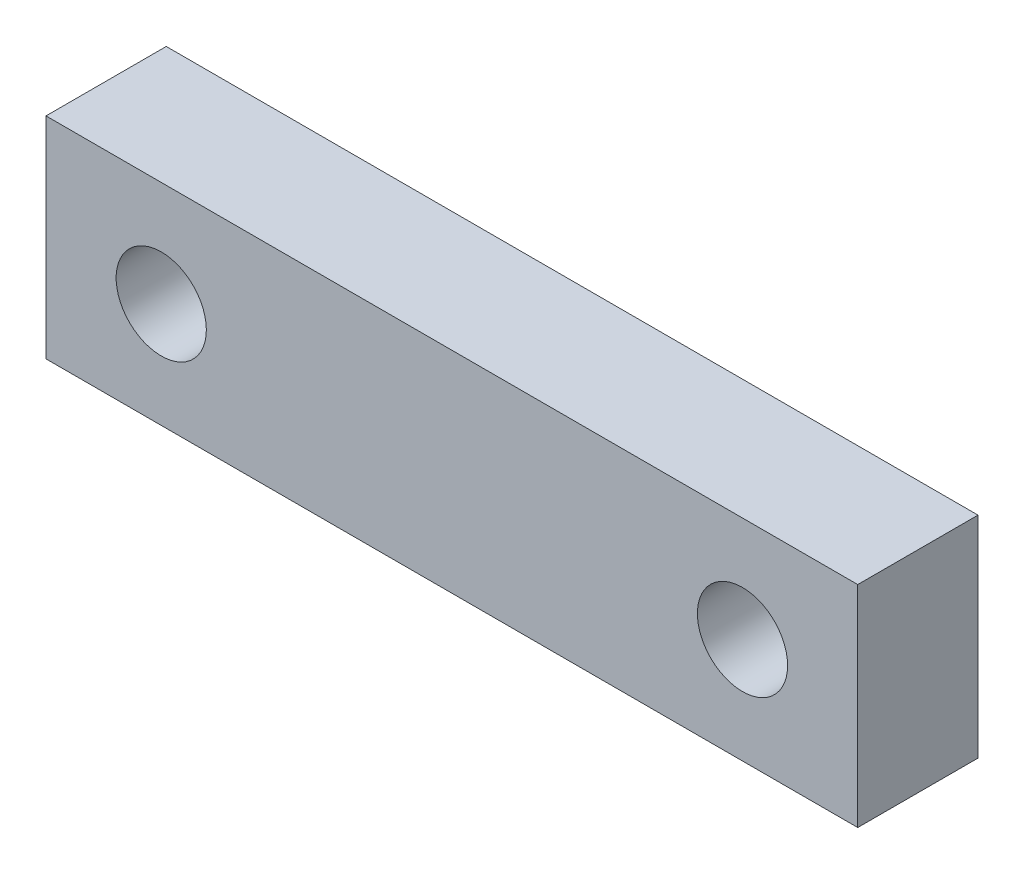
SolidWorks part; units mm, degrees
ref_plane "Front Plane" through (0, 0, 0) normal (0, 0, 1) x (1, 0, 0)
ref_plane "Top Plane" through (0, 0, 0) normal (0, 1, 0) x (1, 0, 0)
ref_plane "Right Plane" through (0, 0, 0) normal (1, 0, 0) x (0, 0, -1)
sketch "Sketch1" plane through (0, 0, 0) normal (0, 0, 1) x (1, 0, 0)
  line L0 (-20.25, 5.25) -> (20.25, -5.25) construction
  line L1 (-20.25, 5.25) -> (20.25, 5.25)
  line L2 (-20.25, 5.25) -> (-20.25, -5.25)
  line L3 (-20.25, -5.25) -> (20.25, -5.25)
  line L4 (20.25, 5.25) -> (20.25, -5.25)
  line L5 (-14.5, 0) -> (14.5, 0) construction
  circle A0 centre (-14.5, 0) radius 2.25
  circle A1 centre (14.5, 0) radius 2.25
  dimension "D3" = 4.5
  dimension "D1" = 10.5
  dimension "D2" = 40.5
  dimension "D4" = 29
extrude "Boss-Extrude1" add sketch "Sketch1" along normal blind 3 and the other way blind 3
